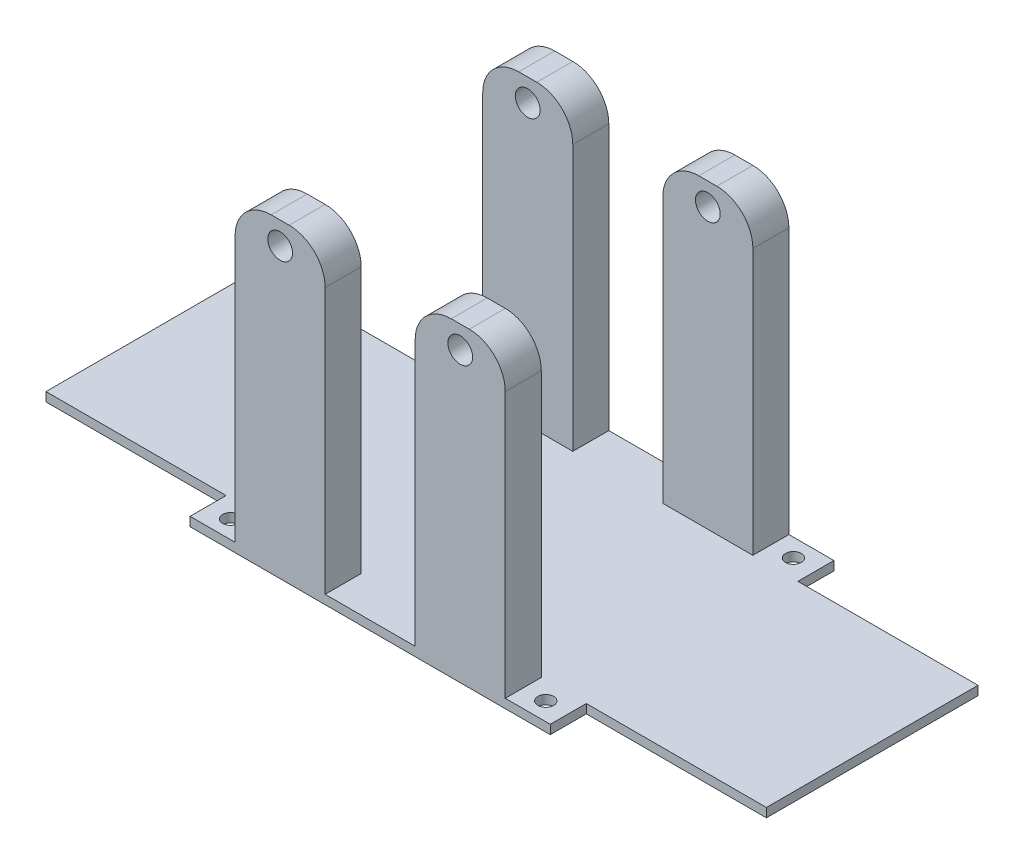
SolidWorks part; units mm, degrees
material "ABS"
ref_plane "Спереди" through (0, 0, 0) normal (0, 0, 1) x (1, 0, 0)
ref_plane "Сверху" through (0, 0, 0) normal (0, 1, 0) x (1, 0, 0)
ref_plane "Справа" through (0, 0, 0) normal (1, 0, 0) x (0, 0, -1)
sketch "Эскиз1" plane through (0, 0, 0) normal (0, 1, 0) x (1, 0, 0)
  line L0 (0, 0) -> (0, 46.182) construction
  line L1 (-80, -23.5) -> (-40, -23.5)
  line L2 (-80, -23.5) -> (-80, 23.5)
  line L3 (-80, 23.5) -> (-40, 23.5)
  line L4 (80, -23.5) -> (80, 23.5)
  line L5 (-80, -23.5) -> (80, 23.5) construction
  line L6 (-80, 23.5) -> (80, -23.5) construction
  line L7 (40, 31.5) -> (-40, 31.5)
  line L8 (40, 31.5) -> (40, 23.5)
  line L10 (-40, 31.5) -> (-40, 23.5)
  line L11 (40, 31.5) -> (-40, 23.5) construction
  line L12 (40, 23.5) -> (-40, 31.5) construction
  line L13 (40, 23.5) -> (80, 23.5)
  line L14 (0, 0) -> (84.9728, 0) construction
  line L15 (40, -31.5) -> (40, -23.5)
  line L16 (40, -31.5) -> (-40, -31.5)
  line L17 (-40, -31.5) -> (-40, -23.5)
  line L18 (40, -23.5) -> (80, -23.5)
  circle A0 centre (-35, 27.5) radius 1.75
  circle A1 centre (35, 27.5) radius 1.75
  circle A2 centre (35, -27.5) radius 1.75
  circle A3 centre (-35, -27.5) radius 1.75
  point P0 (0, 0)
  point P6 (0, 27.5)
  dimension "D5" = 5
  dimension "D7" = 3.5
  dimension "D1" = 160
  dimension "D2" = 47
  dimension "D3" = 8
  dimension "D4" = 80
  dimension "D6" = 4
extrude "Бобышка-Вытянуть1" add sketch "Эскиз1" along normal blind 2
sketch "Эскиз2" plane through (0, 2, 0) normal (0, 1, 0) x (1, 0, 0)
  line L0 (-80, 0) -> (80, 0) construction
  line L1 (-80, 23.5) -> (-80, -23.5) construction
  line L2 (80, -23.5) -> (80, 23.5) construction
  line L3 (0, -31.5) -> (0, 31.5) construction
  line L4 (-40, -31.5) -> (40, -31.5) construction
  line L5 (40, 31.5) -> (-40, 31.5) construction
  line L6 (30, -23.5) -> (10, -23.5)
  line L7 (-30, -31.5) -> (-10, -31.5)
  line L8 (-30, -31.5) -> (-30, -23.5)
  line L9 (-30, -23.5) -> (-10, -23.5)
  line L10 (-10, -31.5) -> (-10, -23.5)
  line L11 (10, -31.5) -> (10, -23.5)
  line L12 (30, -31.5) -> (10, -31.5)
  line L13 (30, -31.5) -> (30, -23.5)
  line L14 (30, 31.5) -> (30, 23.5)
  line L15 (30, 31.5) -> (10, 31.5)
  line L16 (10, 31.5) -> (10, 23.5)
  line L17 (30, 23.5) -> (10, 23.5)
  line L18 (-30, 23.5) -> (-10, 23.5)
  line L19 (-10, 31.5) -> (-10, 23.5)
  line L20 (-30, 31.5) -> (-10, 31.5)
  line L21 (-30, 31.5) -> (-30, 23.5)
  dimension "D1" = 20
  dimension "D2" = 8
  dimension "D3" = 10
extrude "Бобышка-Вытянуть2" add sketch "Эскиз2" along normal blind 67
sketch "Эскиз3" plane through (0, 0, 31.5) normal (0, 0, 1) x (1, 0, 0)
  line L0 (-30, 69) -> (-30, 2) construction
  line L1 (-30, 69) -> (-10, 69) construction
  line L2 (0, 0) -> (0, 72.9909) construction
  circle A0 centre (-20, 64) radius 2.75
  circle A1 centre (20, 64) radius 2.75
  dimension "D1" = 5.5
  dimension "D2" = 10
  dimension "D3" = 5
extrude "Вырез-Вытянуть1" cut sketch "Эскиз3" against normal through all and the other way through all
fillet "Скругление1" radius 8 8 edges at (30, 69, -27.5) (10, 69, -27.5) (-30, 69, -27.5) (-30, 69, 27.5) (10, 69, 27.5) (30, 69, 27.5) (-10, 69, -27.5) (-10, 69, 27.5)
